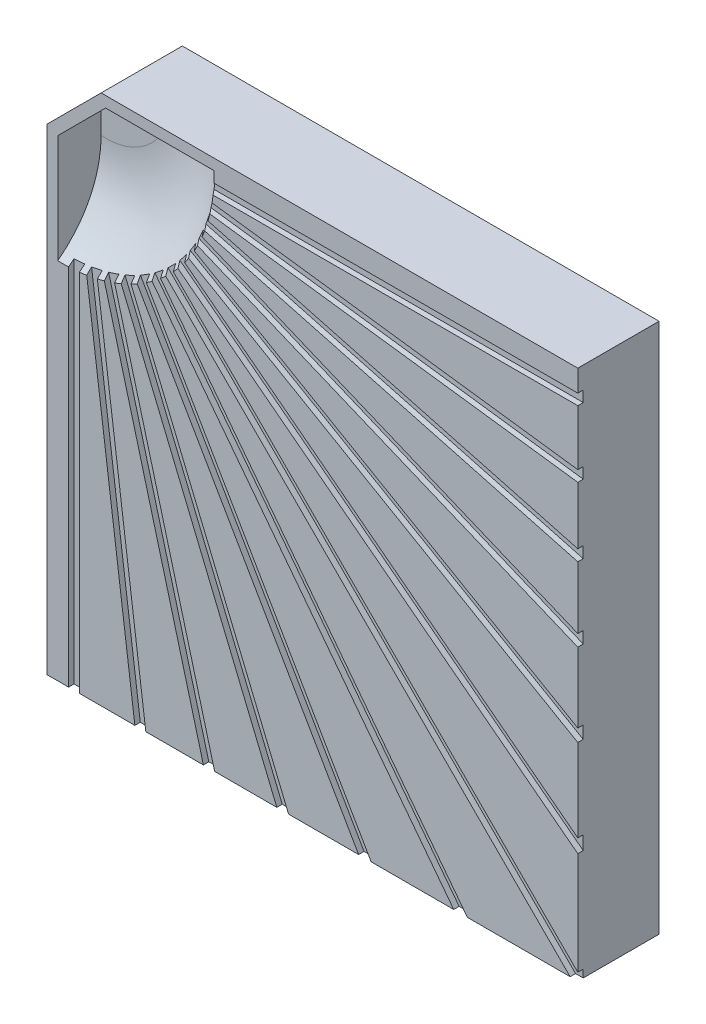
SolidWorks part; units mm, degrees
material "PET"
ref_plane "Front Plane" through (0, 0, 0) normal (1, 0, 0) x (0, 1, 0)
ref_plane "Top Plane" through (0, 0, 0) normal (0, 0, 1) x (0, 1, 0)
ref_plane "Right Plane" through (0, 0, 0) normal (0, 1, 0) x (-1, 0, 0)
sketch "Sketch1" plane through (0, 0, 0) normal (0, 0, 1) x (0, 1, 0)
  line L0 (44, 49) -> (49, 44)
  line L1 (0, 0) -> (49, 0)
  line L2 (0, 0) -> (0, 49)
  line L3 (0, 49) -> (44, 49)
  line L4 (49, 0) -> (49, 44)
  point P1 (49, 49)
  dimension "D1" = 49
extrude "Boss-Extrude1" add sketch "Sketch1" along normal blind 7.5
sketch "Sketch4" plane through (0, 0, 7.5) normal (0, 0, 1) x (1, 0, 0)
  line L0 (-48, 33.5858) -> (-48, 43.5858)
  line L1 (-48, 43.5858) -> (-43.5858, 48)
  line L2 (-43.5858, 48) -> (-33.5858, 48)
  line L3 (-49, 44) -> (-49, 0) construction
  line L4 (-44, 49) -> (-49, 44) construction
  line L5 (0, 49) -> (-44, 49) construction
  arc A0 (-48, 33.5858) -> (-33.5858, 48) centre (-47.5795, 47.5795) ccw
  dimension "D4" = 10
  dimension "D5" = 14
  dimension "D1" = 1
  dimension "D2" = 1
  dimension "D3" = 1
extrude "Cut-Extrude1" cut sketch "Sketch4" against normal blind 4
fillet "Fillet1" radius 10 1 edges at (-37.68, 37.68, 3.5)
sketch "Sketch2" plane through (0, 0, 7.5) normal (0, 0, 1) x (1, 0, 0)
  line L0 (-47, -35.4142) -> (-47, 44.5858)
  line L3 (-49, 44) -> (-49, 0) construction
  line L4 (-44, 49) -> (-49, 44) construction
  dimension "D1" = 2
  dimension "D2" = 1
  dimension "D3" = 80
extrude "Cut-Extrude-Thin2" cut sketch "Sketch2" against normal blind 0.5 and the other way through all thin thin type one direction wall 1
sketch "Sketch3" plane through (-46.5, 46.5, 0) normal (-0.7071, 0.7071, 0) x (-0.7071, -0.7071, 0)
  line L0 (0, 0) -> (0, 7.5) construction
  line L1 (-3.5355, 7.5) -> (3.5355, 7.5) construction
pattern_circular "CirPattern1" count 13 every 7.5 about axis through (-46.5, 46.5, 0) along (0, 0, 1) of "Cut-Extrude-Thin2"
sketch "Sketch5" plane through (0, 0, 0) normal (0, 0, 1) x (0, 1, 0)
  line L0 (44, 49) -> (0, 49) construction
  line L1 (0, 26.6979) -> (0, 20.2306) construction
  circle A0 centre (24.5, 26.5) radius 2
  dimension "D3" = 4
  dimension "D1" = 22.5
  dimension "D2" = 24.5
extrude "Cut-Extrude2" cut sketch "Sketch5" along normal blind 2
